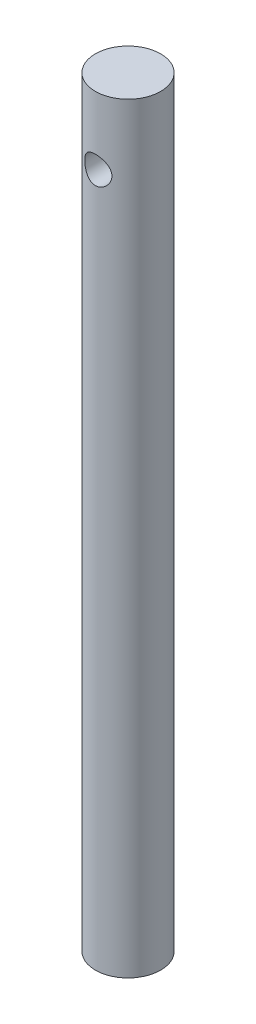
SolidWorks part; units mm, degrees
material "AISI 1035 Steel (SS)"
ref_plane "Front Plane" through (0, 0, 0) normal (0, 0, 1) x (1, 0, 0)
ref_plane "Top Plane" through (0, 0, 0) normal (0, 1, 0) x (1, 0, 0)
ref_plane "Right Plane" through (0, 0, 0) normal (1, 0, 0) x (0, 0, -1)
sketch "Sketch1" plane through (0, 0, 0) normal (0, 0, 1) x (1, 0, 0)
  line L0 (0, 0) -> (0, 140)
  line L1 (0, 140) -> (-6, 140)
  line L2 (-6, 140) -> (-6, 0)
  line L3 (-6, 0) -> (0, 0)
  dimension "D1" = 6
  dimension "D2" = 140
revolve "Revolve1" add sketch "Sketch1" angle 360 about L0
sketch "Sketch2" plane through (0, 0, 0) normal (0, 0, 1) x (1, 0, 0)
  line L0 (-6, 0) -> (6, 0) construction
  line L1 (0, -1000) -> (0, 49000) construction
  circle A0 centre (0, 20) radius 5
  dimension "D1" = 10
  dimension "D2" = 20
sketch "Sketch4" plane through (0, 0, 0) normal (0, 0, 1) x (1, 0, 0)
  line L0 (6, 140) -> (-6, 140) construction
  circle A0 centre (0, 127.5) radius 2.5
  dimension "D1" = 5
  dimension "D2" = 12.5
extrude "Cut-Extrude2" cut sketch "Sketch4" against normal through all both and the other way through all
equation "\"ShaftDiameter\"= 12mm"
equation "\"D5@Sketch1\" = \"ShaftDiameter\""
equation "\"PendulumDiameter\"=12mm"
equation "\"PendulumLength\"= 140mm"
equation "\"D1@Sketch1\"=\"PendulumDiameter\"/2"
equation "\"EncoderOuterDiameter\"=1.5"
equation "\"EncoderShaftDiameter\"= 6mm"
equation "\"EncoderShaftLength\"=15mm+.5in+3mm"
equation "\"PendulumHolderangle\"=60"
equation "\"PendulumholderBottomHeight\"= 75"
equation "\"D3@Sketch1\"=\"PendulumholderBottomHeight\""
equation "\"PendulumholderBottomWidth\"= 75"
equation "\"D4@Sketch1\"=\"PendulumholderBottomWidth\""
equation "\"PendulumholderHeight\"=25"
equation "\"BearingOutsideDiameter\"=21mm"
equation "\"D2@Sketch1\"=\"PendulumLength\""
